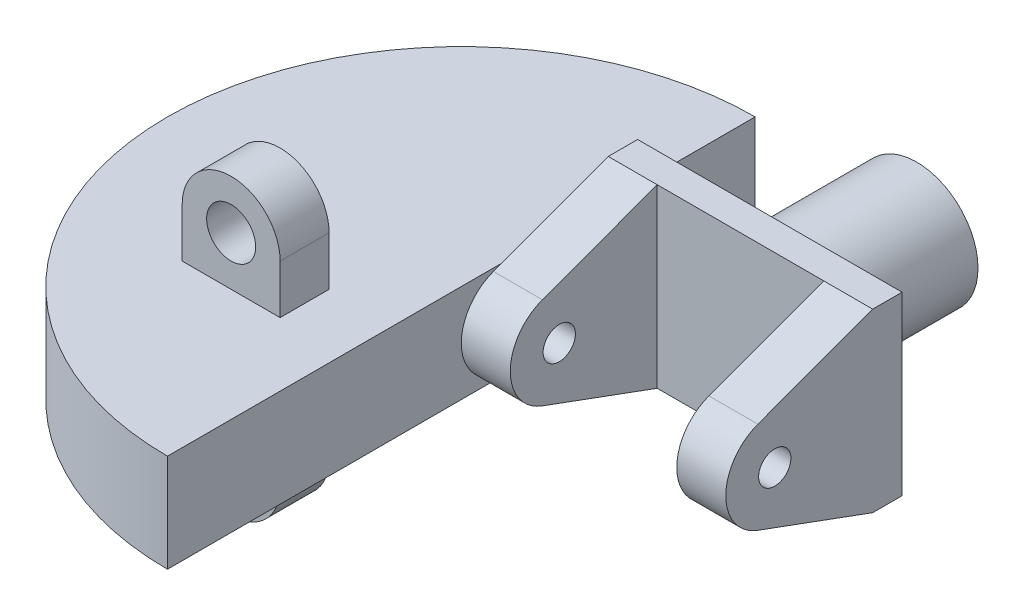
SolidWorks part; units mm, degrees
ref_plane "正面(Front)" through (0, 0, 0) normal (0, 0, 1) x (1, 0, 0)
ref_plane "平面(Top)" through (0, 0, 0) normal (0, 1, 0) x (1, 0, 0)
ref_plane "右側面(Right)" through (0, 0, 0) normal (1, 0, 0) x (0, 0, -1)
sketch "ｽｹｯﾁ1" plane through (0, 0, 0) normal (0, 0, 1) x (1, 0, 0)
  circle A0 centre (0, 0) radius 6.25
  dimension "D1" = 12.5
extrude "ﾎﾞｽ - 押し出し1" add sketch "ｽｹｯﾁ1" along normal blind 15
sketch "ｽｹｯﾁ2" plane through (0, 0, 15) normal (0, 0, 1) x (1, 0, 0)
  line L1 (-13.5, 9) -> (13.5, 9)
  line L2 (-13.5, 9) -> (-13.5, -9)
  line L3 (-13.5, -9) -> (13.5, -9)
  line L4 (13.5, 9) -> (13.5, -9)
  line L5 (-13.5, 9) -> (13.5, -9) construction
  line L6 (-13.5, -9) -> (13.5, 9) construction
  point P0 (0, 0)
  dimension "D1" = 18
  dimension "D2" = 27
extrude "ﾎﾞｽ - 押し出し2" add sketch "ｽｹｯﾁ2" along normal blind 3
sketch "ｽｹｯﾁ3" plane through (0, 0, 0) normal (1, 0, 0) x (0, 0, -1)
  line L0 (-18, 9) -> (-29.724, 4.6934)
  line L1 (-29.724, -4.6934) -> (-18, -9)
  line L2 (0, 0) -> (-40.0433, 0) construction
  line L3 (-18, -9) -> (-18, 9) construction
  line L4 (-18, 9) -> (-18, -9)
  arc A0 (-29.724, 4.6934) -> (-29.724, -4.6934) centre (-28, 0) ccw
  circle A1 centre (-28, 0) radius 1.65
  dimension "D2" = 5
  dimension "D3" = 3.3
  dimension "D1" = 10
extrude "ﾎﾞｽ - 押し出し3" add sketch "ｽｹｯﾁ3" against normal blind 5 from surface starting at face at (13.5, 0, 16.5)
extrude "ﾎﾞｽ - 押し出し4" add sketch "ｽｹｯﾁ3<2>" along normal blind 5 from surface starting at face at (-13.5, 0, 16.5)
sketch "ｽｹｯﾁ3<2>" plane through (0, 0, 0) normal (1, 0, 0) x (0, 0, -1) same geometry as "ｽｹｯﾁ3"
sketch "ｽｹｯﾁ4" plane through (0, 0, 0) normal (0, 1, 0) x (1, 0, 0)
  line L1 (-13.5, -63) -> (-13.5, -3)
  line L3 (-13.5, -18) -> (-13.5, -29.724) construction
  line L4 (8.5, -18) -> (-8.5, -18) construction
  arc A0 (-13.5, -3) -> (-13.5, -63) centre (-13.5, -33) ccw
  dimension "D1" = 30
  dimension "D2" = 15
extrude "ﾎﾞｽ - 押し出し5" add sketch "ｽｹｯﾁ4" along normal mid plane 10
ref_plane "平面1" through (0, 0, 40) normal (0, 0, 1) x (1, 0, 0)
sketch "ｽｹｯﾁ5" plane through (0, 0, 40) normal (0, 0, 1) x (1, 0, 0)
  line L0 (-30, 5) -> (-30, 10)
  line L1 (-13.5, 5) -> (-43.5, 5) construction
  line L2 (-20, 10) -> (-20, 5)
  line L3 (-30, 5) -> (-20, 5)
  arc A0 (-30, 10) -> (-20, 10) centre (-25, 10) cw
  circle A1 centre (-25, 10) radius 2.5
  dimension "D2" = 5
  dimension "D4" = 5
  dimension "D1" = 5
  dimension "D3" = 25
extrude "ﾎﾞｽ - 押し出し6" add sketch "ｽｹｯﾁ5" along normal blind 5
mirror "ﾐﾗｰ1" about plane through (0, 0, 0) normal (0, 1, 0) of "ﾎﾞｽ - 押し出し6"
